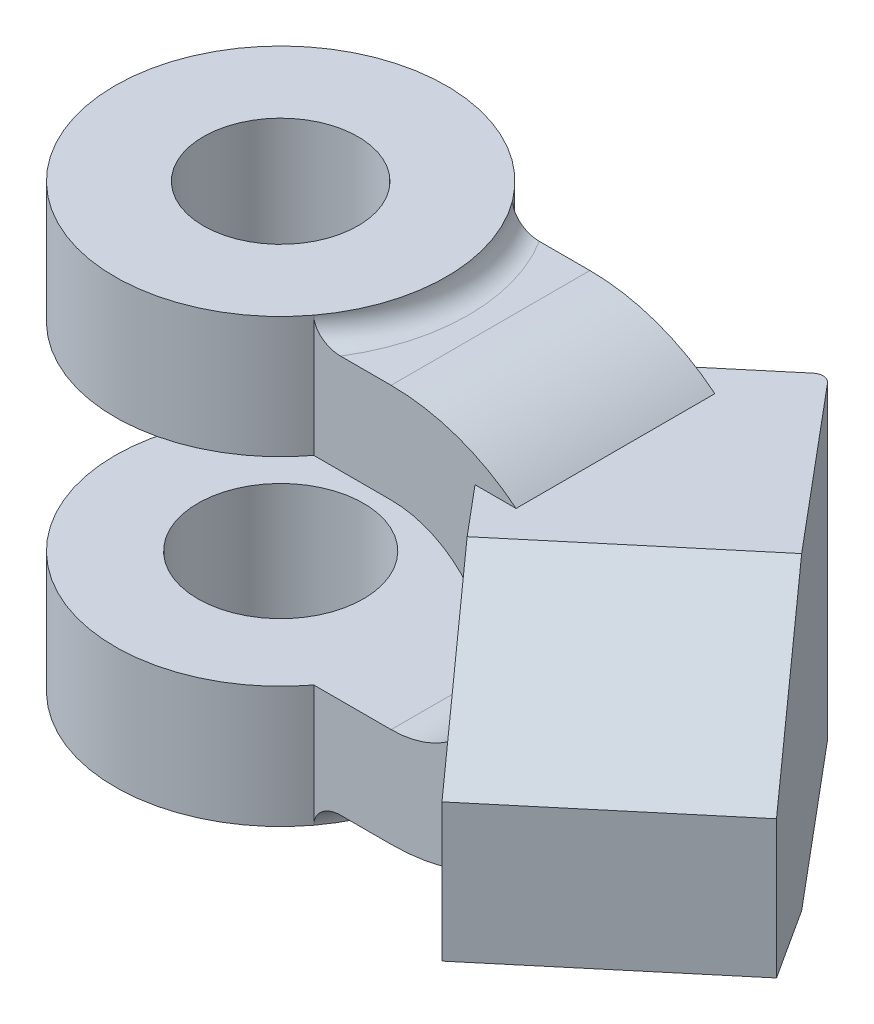
SolidWorks part; units mm, degrees
ref_plane "Front Plane" through (0, 0, 0) normal (0, 0, 1) x (1, 0, 0)
ref_plane "Top Plane" through (0, 0, 0) normal (0, 1, 0) x (1, 0, 0)
ref_plane "Right Plane" through (0, 0, 0) normal (1, 0, 0) x (0, 0, -1)
sketch "Sketch1" plane through (0, 0, 0) normal (0, 0, 1) x (1, 0, 0)
  line L0 (0, 36) -> (0, 18)
  line L1 (0, -18) -> (0, -36)
  arc A0 (0, -18) -> (0, 18) centre (0, 0) ccw
  arc A1 (0, -36) -> (0, 36) centre (0, 0) ccw
extrude "Boss-Extrude1" add sketch "Sketch1" along normal mid plane 36
ref_plane "Plane1" through (0, 18, 0) normal (0, 1, 0) x (1, 0, 0)
sketch "Sketch2" plane through (0, 18, 0) normal (0, 1, 0) x (1, 0, 0)
  circle A0 centre (-38, 0) radius 30
  circle A1 centre (-38, 0) radius 14
  dimension "D2" = 28
  dimension "D3" = 60
  dimension "D1" = 38
extrude "Boss-Extrude2" add sketch "Sketch2" along normal blind 22 separate body
sketch "Sketch4" plane through (0, 0, 0) normal (-1, 0, 0) x (0, 0, 1)
  line L1 (-18, 18) -> (18, 18)
  line L2 (-18, 18) -> (-18, 36)
  line L3 (-18, 36) -> (18, 36)
  line L4 (18, 18) -> (18, 36)
extrude "Boss-Extrude3" add sketch "Sketch4" along normal up to body separate body
sketch "Sketch5" plane through (0, 0, 0) normal (-1, 0, 0) x (0, 0, 1)
  line L1 (-18, -36) -> (18, -36)
  line L2 (-18, -36) -> (-18, -18)
  line L3 (-18, -18) -> (18, -18)
  line L4 (18, -36) -> (18, -18)
ref_plane "Plane2" through (0, -18, 0) normal (0, 1, 0) x (1, 0, 0)
sketch "Sketch6" plane through (0, -18, 0) normal (0, 1, 0) x (1, 0, 0)
  circle A0 centre (-38, 0) radius 15
  circle A1 centre (-38, 0) radius 30
extrude "Boss-Extrude4" add sketch "Sketch6" against normal blind 22 separate body
extrude "Boss-Extrude5" add sketch "Sketch5" along normal up to body separate body
ref_plane "Plane3" through (109, 0, 0) normal (1, 0, 0) x (0, 0, -1)
sketch "Sketch7" plane through (109, 0, 0) normal (1, 0, 0) x (0, 0, -1)
  circle A0 centre (0, 0) radius 15
extrude "Boss-Extrude6" add sketch "Sketch7" along normal blind 22 separate body
sketch "Sketch9" plane through (109, 0, 0) normal (1, 0, 0) x (0, 0, -1)
  line L1 (-7.4558, 18) -> (-18, 7.4558)
  line L2 (-18, 7.4558) -> (-18, -7.4558)
  line L3 (-18, -7.4558) -> (-7.4558, -18)
  line L4 (-7.4558, -18) -> (7.4558, -18)
  line L5 (7.4558, -18) -> (18, -7.4558)
  line L6 (18, -7.4558) -> (18, 7.4558)
  line L7 (18, 7.4558) -> (7.4558, 18)
  line L8 (7.4558, 18) -> (-7.4558, 18)
  circle A0 centre (0, 0) radius 18 construction
  point P1 (-18, 0)
  dimension "D1" = 18
  dimension "D2" = 36
extrude "Boss-Extrude8" add sketch "Sketch9" against normal blind 45
sketch "Sketch10" plane through (64, 0, 0) normal (-1, 0, 0) x (0, 0, 1)
  line L1 (-18, -18) -> (18, -18)
  line L2 (-18, -18) -> (-18, 18)
  line L3 (-18, 18) -> (18, 18)
  line L4 (18, -18) -> (18, 18)
  line L5 (-18, -18) -> (18, 18) construction
  line L6 (-18, 18) -> (18, -18) construction
  point P0 (0, 0)
  dimension "D1" = 36
  dimension "D2" = 36
extrude "Boss-Extrude9" add sketch "Sketch10" along normal up to next
fillet "Fillet1" radius 7.45 4 edges at (64, -12.7279, -12.7279) (64, 12.7279, -12.7279) (64, -12.7279, 12.7279) (64, 12.7279, 12.7279)
fillet "Fillet2" radius 4 2 edges at (-8, -36, 0) (-8, 36, 0)
scale "Scala1" scale about centroid uniform scaling yes scale factor 0.1
ref_plane "Piano1" through (17.7139, 0, -14.8637) normal (0.766, 0, -0.6428) x (0, 1, 0)
sketch "Schizzo1" plane through (17.7139, 0, -14.8637) normal (0.766, 0, -0.6428) x (0, 1, 0)
  line L1 (-8.3333, 11.3982) -> (8.9288, 11.3982)
  line L2 (-8.3333, 11.3982) -> (-8.3333, 24.2225)
  line L3 (-8.3333, 24.2225) -> (8.9288, 24.2225)
  line L4 (8.9288, 11.3982) -> (8.9288, 24.2225)
extrude "Taglio-Estrusione1" cut sketch "Schizzo1" against normal mid plane 11 contours L3 L4 L1 L2
sketch "Schizzo2" plane through (17.7139, 0, -14.8637) normal (0.766, 0, -0.6428) x (0, 1, 0)
  line L0 (-1.6034, 12.4384) -> (-1.6034, 16.6747) construction
  line L1 (-1.0534, 18.6379) -> (1.4438, 18.6379)
  line L2 (-2.6034, 14.9379) -> (-2.6034, 10.9384)
  line L3 (-2.6034, 10.9384) -> (2.9966, 10.9384)
  line L4 (2.9966, 14.9379) -> (2.9966, 10.9384)
  line L5 (1.9966, 16.6747) -> (1.9966, 12.4384) construction
  line L6 (1.1105, 17.1379) -> (-0.7174, 17.1379) construction
  line L7 (1.9966, 12.4384) -> (-1.6034, 12.4384) construction
  line L8 (-1.0534, 18.6379) -> (-2.6034, 14.9379)
  line L9 (1.4438, 18.6379) -> (2.9966, 14.9379)
  dimension "D1" = 1
  dimension "D2" = 1.5
  dimension "D3" = 1.5
  dimension "D4" = 1
  dimension "D5" = 3.7
  dimension "D6" = 3.7
  dimension "D7" = 1.5528
  dimension "D8" = 1.55
extrude "Estrusione-Estrusione2" add sketch "Schizzo2" against normal blind 9.5
ref_plane "Piano2" through (27.3158, 2.9966, -3.4206) normal (0.5927, -0.387, 0.7064) x (0.8054, 0.2848, -0.5198)
sketch "Schizzo4" plane through (17.7139, 0, -14.8637) normal (0.766, 0, -0.6428) x (0, 1, 0)
  line L1 (-13.5124, 26.9046) -> (11.5409, 26.9046)
  line L2 (-13.5124, 26.9046) -> (-13.5124, -3.5595)
  line L3 (-13.5124, -3.5595) -> (11.5409, -3.5595)
  line L4 (11.5409, 26.9046) -> (11.5409, -3.5595)
extrude "Taglio-Estrusione2" cut sketch "Schizzo4" against normal blind 5.2
fillet "Raccordo1" radius 1.5 1 edges at (17.4676, 0.1966, -0.3779)
fillet "Raccordo5" radius 0.2 1 edges at (20.7616, 0.1966, -3.1419)
